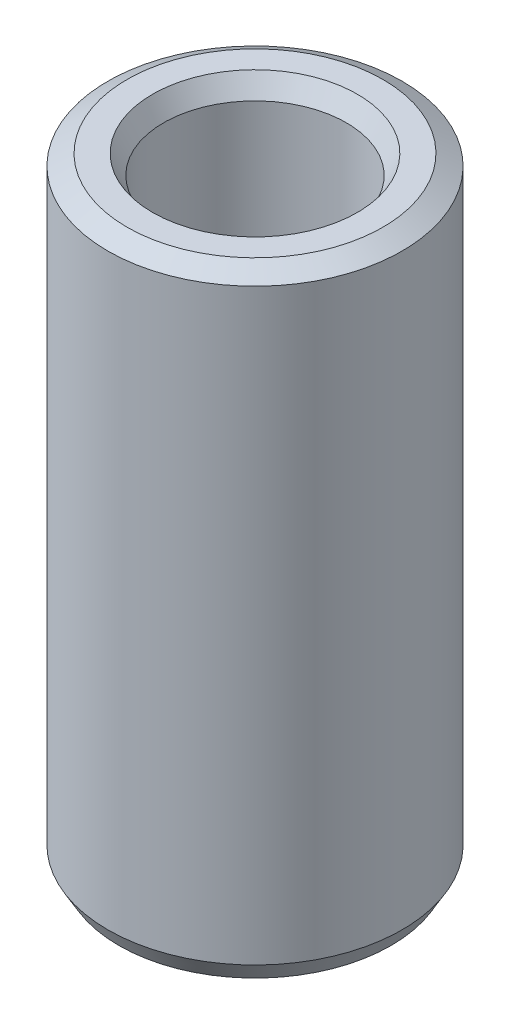
SolidWorks part; units mm, degrees
ref_plane "Front Plane" through (0, 0, 0) normal (0, 0, 1) x (1, 0, 0)
ref_plane "Top Plane" through (0, 0, 0) normal (0, 1, 0) x (1, 0, 0)
ref_plane "Right Plane" through (0, 0, 0) normal (1, 0, 0) x (0, 0, -1)
sketch "Sketch1" plane through (0, 0, 0) normal (0, 1, 0) x (1, 0, 0)
  circle A0 centre (0, 0) radius 30
  dimension "SLEEVE_OD" = 60
extrude "Boss-Extrude1" add sketch "Sketch1" along normal blind 126.0147
sketch "Sketch2" plane through (0, 0, 0) normal (0, 1, 0) x (1, 0, 0)
  circle A0 centre (0, 0) radius 18.63
  dimension "BORE_D" = 37.26
extrude "Cut-Extrude1" cut sketch "Sketch2" along normal through all
chamfer "Chamfer1" distance 2.2553 angle 60 4 edges at (0, 126.0147, 18.63) (0, 0, 18.63) (0, 0, 30) (0, 126.0147, 30) first distance on face at (0, 126.0147, 18.63) first distance on face at (0, 0, 18.63) first distance on face at (0, 126.0147, 30)
